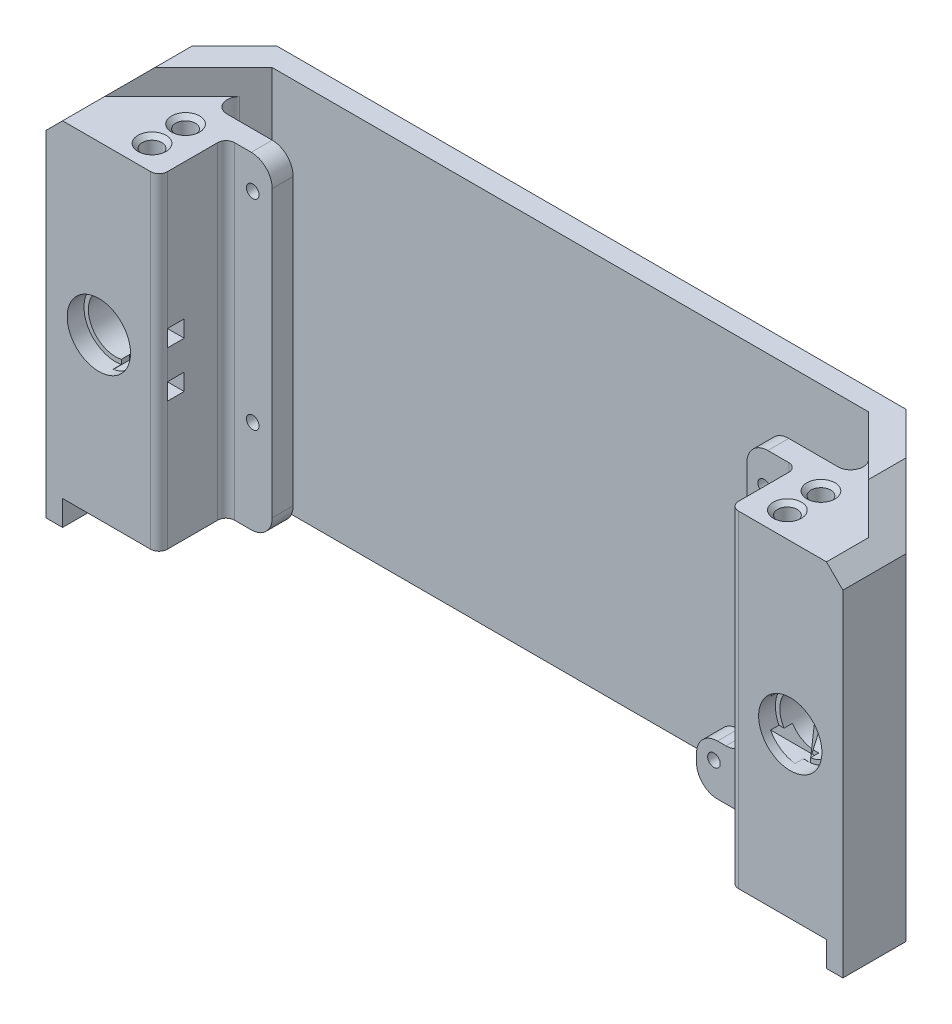
SolidWorks part; units mm, degrees
ref_plane "Front Plane" through (0, 0, 0) normal (0, 0, 1) x (1, 0, 0)
ref_plane "Top Plane" through (0, 0, 0) normal (0, 1, 0) x (1, 0, 0)
ref_plane "Right Plane" through (0, 0, 0) normal (1, 0, 0) x (0, 0, -1)
sketch "Sketch1" plane through (0, 0, 0) normal (0, 0, 1) x (1, 0, 0)
  line L1 (-95, 45) -> (95, 45)
  line L2 (-95, 45) -> (-95, -45)
  line L3 (-95, -45) -> (95, -45)
  line L4 (95, 45) -> (95, -45)
  line L5 (-95, 45) -> (95, -45) construction
  line L6 (-95, -45) -> (95, 45) construction
  point P0 (0, 0)
  point P6 (0, 0)
  dimension "D2" = 190
  dimension "D4" = 90
extrude "Boss-Extrude1" add sketch "Sketch1" along normal blind 5
sketch "Sketch2" plane through (0, 0, 5) normal (0, 0, 1) x (1, 0, 0)
  line L0 (-95, -45) -> (95, -45) construction
  line L1 (-95, 45) -> (-91.1, 45)
  line L2 (-95, 45) -> (-95, -45)
  line L3 (-95, -45) -> (-91.1, -45)
  line L4 (-91.1, 45) -> (-91.1, -45)
  line L5 (0, 0) -> (0, 45) construction
  line L6 (95, 45) -> (-95, 45) construction
  line L7 (95, -45) -> (91.1, -45)
  line L8 (91.1, 45) -> (91.1, -45)
  line L9 (95, 45) -> (91.1, 45)
  line L10 (95, 45) -> (95, -45)
  dimension "D1" = 3.9
extrude "Boss-Extrude2" add sketch "Sketch2" along normal blind 30
sketch "Sketch3" plane through (0, 45, 0) normal (0, 1, 0) x (1, 0, 0)
  line L0 (-91.1, -35) -> (-91.1, -5) construction
  line L1 (-91.1, -14) -> (-57.1, -14)
  line L2 (-91.1, -14) -> (-91.1, -19)
  line L3 (-91.1, -19) -> (-57.1, -19)
  line L4 (-57.1, -14) -> (-57.1, -19)
  line L5 (91.1, -35) -> (91.1, -5) construction
  line L6 (91.1, -14) -> (44.1, -14)
  line L7 (91.1, -14) -> (91.1, -19)
  line L8 (91.1, -19) -> (44.1, -19)
  line L9 (44.1, -14) -> (44.1, -19)
  line L10 (91.1, -5) -> (-91.1, -5) construction
  dimension "D1" = 9
  dimension "D2" = 9
  dimension "D3" = 5
  dimension "D4" = 5
  dimension "D5" = 34
  dimension "D6" = 47
extrude "Boss-Extrude3" add sketch "Sketch3" against normal up to surface (90 mm away) up to face at (0, -45, 18.75)
sketch "Sketch4" plane through (0, 0, 19) normal (0, 0, 1) x (1, 0, 0)
  line L0 (91.1, -45) -> (91.1, 45) construction
  line L1 (-91.1, 45) -> (91.1, 45)
  line L2 (-91.1, 45) -> (-91.1, 39)
  line L3 (-91.1, 39) -> (91.1, 39)
  line L4 (91.1, 45) -> (91.1, 39)
  line L5 (0, 0) -> (-91.1, 0) construction
  line L6 (-91.1, -45) -> (-91.1, 45) construction
  line L7 (-91.1, -39) -> (91.1, -39)
  line L8 (91.1, -45) -> (91.1, -39)
  line L9 (-91.1, -45) -> (91.1, -45)
  line L10 (-91.1, -45) -> (-91.1, -39)
  dimension "D1" = 6
extrude "Cut-Extrude1" cut sketch "Sketch4" against normal blind 5
sketch "Sketch5" plane through (0, 0, 19) normal (0, 0, 1) x (1, 0, 0)
  line L0 (0, 0) -> (-61.75, 0) construction
  line L1 (-70.2, 37.38) -> (70.2, 37.38) construction
  line L2 (-70.2, 37.38) -> (-70.2, -37.38) construction
  line L3 (-70.2, -37.38) -> (70.2, -37.38) construction
  line L4 (70.2, 37.38) -> (70.2, -37.38) construction
  line L5 (-70.2, 37.38) -> (70.2, -37.38) construction
  line L6 (-70.2, -37.38) -> (70.2, 37.38) construction
  line L7 (-61.75, 0) -> (-61.75, 31.13) construction
  line L8 (-61.75, 0) -> (-61.75, -16.61) construction
  line L9 (48.25, 0) -> (60.23, 0) construction
  line L10 (60.23, 0) -> (60.23, 31.13) construction
  line L11 (0, 0) -> (48.25, 0) construction
  line L12 (48.25, 0) -> (48.25, -31.38) construction
  circle A0 centre (-61.75, 31.13) radius 1.5
  circle A1 centre (-61.75, -16.61) radius 1.5
  circle A2 centre (60.23, 31.13) radius 1.5
  circle A3 centre (48.25, -31.38) radius 1.5
  point P0 (0, 0)
  dimension "D10" = 3
  dimension "D11" = 3
  dimension "D12" = 3
  dimension "D13" = 3
  dimension "D1" = 140.4
  dimension "D2" = 74.76
  dimension "D3" = 61.75
  dimension "D4" = 31.13
  dimension "D5" = 16.61
  dimension "D6" = 60.23
  dimension "D7" = 31.13
  dimension "D8" = 48.25
  dimension "D9" = 31.38
extrude "Cut-Extrude2" cut sketch "Sketch5" against normal up to surface (5 mm away) up to face at (67.6, 0, 14)
sketch "Sketch6" plane through (0, 0, 19) normal (0, 0, 1) x (1, 0, 0)
  line L1 (44.1, 39) -> (56.1, 39)
  line L2 (44.1, 39) -> (44.1, -27)
  line L3 (44.1, -27) -> (56.1, -27)
  line L4 (56.1, 39) -> (56.1, -27)
  dimension "D1" = 12
  dimension "D2" = 66
extrude "Cut-Extrude3" cut sketch "Sketch6" against normal up to surface (5 mm away) up to face at (46.75, -31.38, 14)
chamfer "Chamfer6" distance 20 angle 45 4 edges at (91.1, 0, 5) (95, 0, 0) (-95, 0, 0) (-91.1, 0, 5)
sketch "Sketch7" plane through (0, 39, 0) normal (0, 1, 0) x (1, 0, 0)
  line L0 (-85.1, -19) -> (-91.1, -25)
  line L1 (-91.1, -25) -> (-91.1, -35)
  line L2 (-91.1, -35) -> (-68.1, -35)
  line L3 (-68.1, -35) -> (-68.1, -19)
  line L4 (-85.1, -19) -> (-57.1, -19) construction
  line L5 (-68.1, -19) -> (-85.1, -19)
  line L6 (0, 0) -> (0, -5) construction
  line L7 (71.1, -5) -> (-71.1, -5) construction
  line L8 (68.1, -35) -> (68.1, -19)
  line L9 (91.1, -35) -> (68.1, -35)
  line L10 (91.1, -25) -> (91.1, -35)
  line L11 (85.1, -19) -> (91.1, -25)
  line L12 (68.1, -19) -> (85.1, -19)
  dimension "D1" = 23
extrude "Boss-Extrude4" add sketch "Sketch7" against normal up to surface (78 mm away) up to face at (-69.85, -39, 16.5)
fillet "Fillet4" radius 5 6 edges at (-57.1, -39, 16.5) (-57.1, 39, 16.5) (56.1, 39, 16.5) (44.1, -39, 16.5) (44.1, -27, 16.5) (56.1, -27, 16.5)
fillet "Fillet5" radius 2 4 edges at (-68.1, 0, 35) (68.1, 0, 35) (68.1, 0, 19) (-68.1, 0, 19)
fillet "Fillet6" radius 3 2 edges at (-80.1, 0, 14) (80.1, 0, 14)
sketch "Sketch9" plane through (0, 0, 35) normal (0, 0, 1) x (1, 0, 0)
  line L6 (0, 0) -> (0, -45) construction
  line L7 (-71.1, -45) -> (71.1, -45) construction
  line L8 (-95, 45) -> (-95, -45) construction
  line L9 (-95, 39) -> (-82.45, 39) construction
  line L10 (-95, 39) -> (-95, -0.9074) construction
  line L11 (-95, -0.9074) -> (-82.45, -0.9074) construction
  line L12 (-82.45, 39) -> (-82.45, -0.9074) construction
  line L13 (-91.1, 39) -> (-70.1, 39) construction
  circle A0 centre (-82.45, -0.9074) radius 6.5
  circle A1 centre (82.45, -0.9074) radius 6.5
  dimension "D3" = 13
  dimension "D1" = 39.9074
  dimension "D2" = 12.55
extrude "Cut-Extrude4" cut sketch "Sketch9" against normal blind 10
sketch "Sketch10" plane through (0, 0, 35) normal (0, 0, 1) x (1, 0, 0)
  circle A0 centre (-82.45, -0.9074) radius 7.55
  circle A1 centre (82.45, -0.9074) radius 7.55
  dimension "D1" = 15.1
  dimension "D2" = 15.1
extrude "Cut-Extrude5" cut sketch "Sketch10" against normal blind 4
sketch "Sketch12" plane through (-68.1, 0, 0) normal (1, 0, 0) x (0, 0, -1)
  line L0 (-33, -4.4074) -> (-29, -4.4074)
  line L1 (-33, 39) -> (-23, 39) construction
  line L2 (-33, 39) -> (-33, -0.9074) construction
  line L3 (-33, -0.9074) -> (-23, -0.9074) construction
  line L4 (-23, 39) -> (-23, -0.9074) construction
  line L5 (-33, 6.5926) -> (-23, 6.5926) construction
  line L6 (-33, 6.5926) -> (-33, -8.4074) construction
  line L7 (-33, -8.4074) -> (-23, -8.4074) construction
  line L8 (-23, 6.5926) -> (-23, -8.4074) construction
  line L9 (-33, 6.5926) -> (-23, -8.4074) construction
  line L10 (-33, -8.4074) -> (-23, 6.5926) construction
  line L11 (-33, 6.5926) -> (-29, 6.5926)
  line L12 (-33, 6.5926) -> (-33, 2.5926)
  line L13 (-33, 2.5926) -> (-29, 2.5926)
  line L14 (-29, 6.5926) -> (-29, 2.5926)
  line L15 (-29, -8.4074) -> (-29, -4.4074)
  line L16 (-33, -8.4074) -> (-29, -8.4074)
  line L17 (-33, -8.4074) -> (-33, -4.4074)
  point P5 (-28, -0.9074)
  dimension "D1" = 39.9074
  dimension "D2" = 10
  dimension "D3" = 15
  dimension "D4" = 10
  dimension "D5" = 4
  dimension "D6" = 4
extrude "Cut-Extrude6" cut sketch "Sketch12" against normal blind 13 and the other way blind 151.4
sketch "Sketch15" plane through (0, 39, 0) normal (0, 1, 0) x (1, 0, 0)
  line L0 (68.1, -21) -> (68.1, -33) construction
  line L5 (72.8574, -14) -> (61.1, -14) construction
  line L6 (91.1, -35) -> (68.1, -35) construction
  line L7 (91.1, -35) -> (91.1, -14) construction
  line L8 (91.1, -14) -> (68.1, -14) construction
  line L9 (68.1, -35) -> (68.1, -14) construction
  line L10 (68.1, -14) -> (75.7667, -21) construction
  line L11 (75.7667, -21) -> (83.4333, -28) construction
  line L12 (83.4333, -28) -> (91.1, -35) construction
  line L13 (0, 0) -> (0, -5) construction
  line L14 (71.1, -5) -> (-71.1, -5) construction
  line L15 (75.7667, -21) -> (75.7667, -29) construction
  circle A0 centre (75.7667, -21) radius 2.35
  circle A1 centre (83.4333, -28) radius 2.35 construction
  circle A2 centre (-75.7667, -21) radius 2.35
  circle A3 centre (-83.4333, -28) radius 2.35 construction
  circle A4 centre (75.7667, -29) radius 2.35
  circle A5 centre (-75.7667, -29) radius 2.35
  dimension "D1" = 4.7
  dimension "D2" = 4.7
  dimension "D5" = 4.7
  dimension "D3" = 23
  dimension "D4" = 21
  dimension "D6" = 8
extrude "Cut-Extrude7" cut sketch "Sketch15" against normal blind 8
chamfer "Chamfer7" distance 1 angle 45 4 edges at (-75.7667, 39, 18.65) (75.7667, 39, 23.35) (75.7667, 39, 31.35) (-75.7667, 39, 26.65)
sketch "Sketch17" plane through (0, -39, 0) normal (0, -1, 0) x (1, 0, 0)
  line L0 (0, 0) -> (0, 5) construction
  line L1 (91.1, 35) -> (68.1, 35) construction
  line L2 (91.1, 35) -> (91.1, 19) construction
  line L3 (91.1, 19) -> (68.1, 19) construction
  line L4 (68.1, 35) -> (68.1, 19) construction
  line L5 (-71.1, 5) -> (71.1, 5) construction
  line L6 (68.1, 33) -> (68.1, 21) construction
  line L7 (66.1, 19) -> (49.1, 19) construction
  circle A0 centre (79.6, 27) radius 6.1
  circle A1 centre (-79.6, 27) radius 6.1
  dimension "D2" = 12.2
  dimension "D1" = 11.5
  dimension "D3" = 8
  dimension "D4" = 11.5
extrude "Cut-Extrude8" cut sketch "Sketch17" against normal blind 3.2
fillet "Fillet7" radius 0.2 2 edges at (-85.7, -39, 27) (85.7, -39, 27)
chamfer "Chamfer8" distance 9.9 angle 45 2 edges at (-95, 45, 27.5) (95, 45, 27.5)
